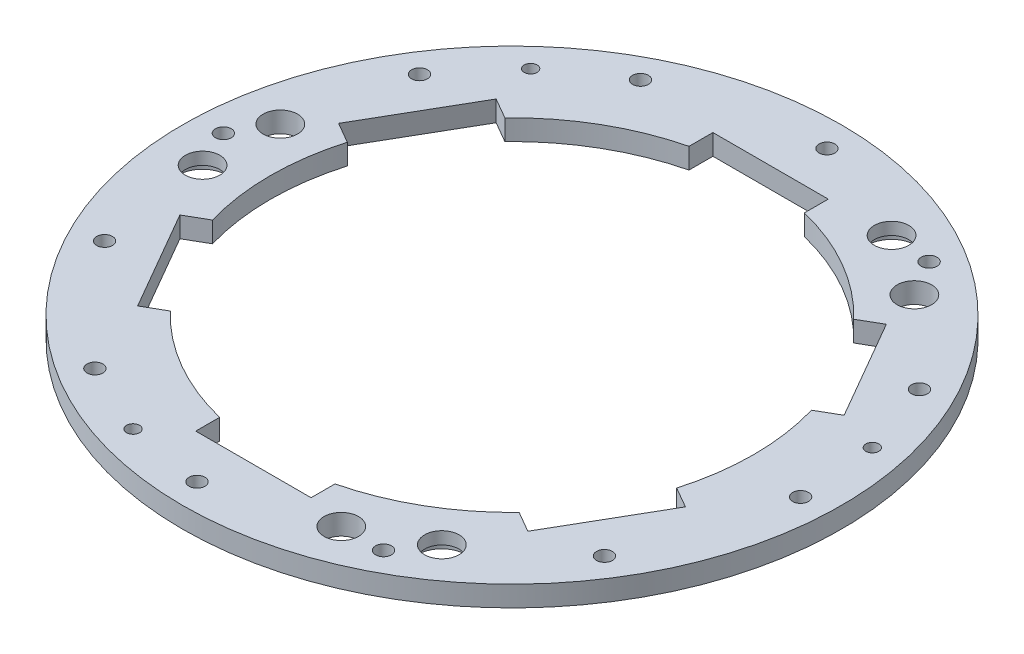
SolidWorks part; units mm, degrees
material "6061 Alloy"
ref_plane "Front Plane" through (0, 0, 0) normal (0, 0, 1) x (1, 0, 0)
ref_plane "Top Plane" through (0, 0, 0) normal (0, 1, 0) x (1, 0, 0)
ref_plane "Right Plane" through (0, 0, 0) normal (1, 0, 0) x (0, 0, -1)
sketch "Sketch1" plane through (0, 0, 0) normal (0, 1, 0) x (1, 0, 0)
  line L0 (-13.335, -54.2656) -> (-13.335, -58.1814)
  line L1 (13.335, -54.2656) -> (13.335, -58.1814)
  line L2 (-13.335, -59.7901) -> (13.335, -59.7901)
  line L3 (13.335, -58.1814) -> (13.335, -59.7901)
  line L4 (-13.335, -58.1814) -> (-13.335, -59.7901)
  line L5 (0, 0) -> (-65.7887, -5.7558) construction
  line L6 (0, 0) -> (-3.0468, -69.7835) construction
  line L7 (0, 0) -> (0, -26.4169) construction
  line L8 (0, 0) -> (-21.0043, -66.6171) construction
  line L9 (-65.0367, 11.4677) -> (0, 0) construction
  circle A0 centre (0, 0) radius 55.88
  circle A1 centre (0, 0) radius 76.2
  circle A2 centre (0, 0) radius 59.69
  circle A3 centre (-3.0468, -69.7835) radius 1.8288
  circle A4 centre (-65.7887, -5.7558) radius 3.9903
  circle A5 centre (-65.0367, 11.4677) radius 3.9903
  circle A6 centre (-21.0043, -66.6171) radius 1.5
  point P24 (0, 0)
  point P29 (0, 0)
  dimension "D1" = 111.76
  dimension "D2" = 152.4
  dimension "D8" = 3.6576
  dimension "D11" = 7.9807
  dimension "D12" = 7.9807
  dimension "D16" = 3
  dimension "D4" = 13.335
  dimension "D5" = 13.335
  dimension "D7" = 69.85
  dimension "D6" = 5.5245
  dimension "D9" = 66.04
  dimension "D10" = 82.5
  dimension "D15" = 15
  dimension "D13" = 2.5
  dimension "D14" = 15
  dimension "D3" = 3.81
extrude "Boss-Extrude1" add sketch "Sketch1" along normal blind 4.7625 contours L1 A2 L0 A0 | A1 A2 A0 region at (-15.0127, 0, 56.2235) region at (-74.0447, 0, 0)
pattern_circular "CirPattern1" count 6 over 360 about axis through (0, 4.7625, 0) along (0, 1, 0) of face at (-13.335, 2.3813, 57.0278) of face at (13.335, 2.3813, 57.0278) of face at (0, 2.3813, 59.7901)
pattern_circular "CirPattern7" count 12 over 360 about axis through (0, 4.7625, 0) along (0, 1, 0) of face at (-3.0468, 4.7625, 71.6123)
sketch "Sketch4" plane through (0, 0, 0) normal (0, -1, 0) x (1, 0, 0)
  line L0 (0, 0) -> (-65.7887, 5.7558) construction
  line L1 (0, 0) -> (0, -39.7137) construction
  circle A0 centre (-65.7887, 5.7558) radius 5.588
  circle A2 centre (-65.7887, 5.7558) radius 3.9903 construction
  circle A3 centre (-65.7887, 5.7558) radius 3.9903
  point P12 (0, 0)
  dimension "D2" = 11.176
extrude "Cut-Extrude1" cut sketch "Sketch4" against normal blind 1.905 contours A0 region at (-71.2186, 0, 5.7558)
pattern_circular "CirPattern2" count 3 over 360 about axis through (0, 0, 0) along (0, 1, 0) of face at (-65.7887, 4.7625, 9.7461) of face at (-65.7887, 1.905, 1.7654) of face at (-65.7887, 1.905, 0.1678) of face at (-65.0367, 4.7625, -7.4774) of face at (-21.0043, 4.7625, 68.1171)
sketch "Sketch5" plane through (0, 4.7625, 0) normal (0, 1, 0) x (1, 0, 0)
  line L0 (0, 0) -> (-20.0894, -55.1952)
  line L1 (0, 0) -> (0, -18.6852)
  line L2 (-16.5968, -53.0258) -> (-18.2257, -57.5011) construction
  line L3 (-18.2257, -57.5011) -> (-22.9993, -55.7636) construction
  line L4 (-22.9993, -55.7636) -> (-21.3704, -51.2884) construction
  line L5 (-59.7924, -7.9638) -> (-55.1022, -7.1368)
  line L6 (-54.2201, -12.1397) -> (-58.9103, -12.9667)
  line L7 (-58.9103, -12.9667) -> (-59.7924, -7.9638)
  line L8 (-36.7931, 47.7998) -> (-33.7318, 44.1515)
  line L9 (-37.6233, 40.8862) -> (-40.6846, 44.5345)
  line L10 (-40.6846, 44.5345) -> (-36.7931, 47.7998)
  line L11 (22.9993, 55.7636) -> (21.3704, 51.2884)
  line L12 (16.5968, 53.0258) -> (18.2257, 57.5011)
  line L13 (18.2257, 57.5011) -> (22.9993, 55.7636)
  line L14 (59.7924, 7.9638) -> (55.1022, 7.1368)
  line L15 (54.2201, 12.1397) -> (58.9103, 12.9667)
  line L16 (58.9103, 12.9667) -> (59.7924, 7.9638)
  line L17 (36.7931, -47.7998) -> (33.7318, -44.1515)
  line L18 (37.6233, -40.8862) -> (40.6846, -44.5345)
  line L19 (40.6846, -44.5345) -> (36.7931, -47.7998)
  circle A0 centre (0, 0) radius 55.5625
  circle A1 centre (0, 0) radius 58.7375 construction
  circle A2 centre (0, 0) radius 55.5625
  circle A3 centre (0, 0) radius 55.5625
  circle A4 centre (0, 0) radius 55.5625
  circle A5 centre (0, 0) radius 55.5625
  circle A6 centre (0, 0) radius 55.5625
  circle A7 centre (0, 0) radius 76.2
  circle A8 centre (0, 0) radius 63.5
  point P38 (0, 0)
  dimension "D1" = 111.125
  dimension "D3" = 20
  dimension "D4" = 2.54
  dimension "D5" = 4.7625
  dimension "D6" = 2.54
  dimension "D2" = 3.175
  dimension "D8" = 12.7
  dimension "D7" = 6
split line "Split Line1" [suppressed]
equation "\"Middle Coupler Inner Daimeter\"= 3.875in"
equation "\"Middle Coupler  Wall Thickness\" = 0.25in"
equation "\"Middle Coupler Bottom Thickness\"= 0.2in"
equation "\"Bearing Rail Offset\"= 0.45in"
equation "\"3-56 UNF Tap\"= 0.089in"
equation "\"3-56 UNF Clearance\"= 0.104in"
equation "\"Ball Bearing Distance\"= 0.03in"
equation "\"D1@Sketch1\"=\"Middle Coupler Inner Daimeter\"+0.5+0.0125*2in"
equation "\"TCA Outer Diameter\" = 6in"
equation "\"D2@Sketch1\"=\"TCA Outer Diameter\""
equation "\"D4@Sketch1\"=0.50 + (0.05/2)"
equation "\"D5@Sketch1\"=\"D4@Sketch1\""
equation "\"D7@Sketch1\"=(\"D2@Sketch1\"-0.5)/2"
equation "\"D8@Sketch1\"=\"6-32 Clearance\""
equation "\"Interstage Aeroframe Wall Thickness\" = 0.072in"
equation "\"Compression Spring OD\"= 0.42in"
equation "\"10-24 Tap\"= 0.157in"
equation "\"10-24 Clearance\"= 0.196in"
equation "\"D2@Sketch4\"=\"Compression Spring OD\"+0.02"
equation "\"D3@Sketch1\"=0.125in+(0.05/2)"
equation "\"Lower Stage Fuselage Wall Thickness\" = 0.25in"
equation "\"6-32 Tap\" = 0.107in"
equation "\"1/4-20 Tap\" = 0.201in"
equation "\"3-48 Tap\"= 0.079in"
equation "\"12-24 Tap\" = 0.177in"
equation "\"3-48 Clearance\" = 0.104in"
equation "\"6-32 Clearance\" = 0.144"
equation "\"D6@Sketch1\"=3/16 + 0.03"
equation "\"D9@Sketch1\"=(\"D2@Sketch1\"+\"D1@Sketch1\")/4+0.1-.1"
equation "\"D1@Sketch5\"=\"Middle Coupler Inner Daimeter\"+0.5"
equation "\"D5@Sketch5\"=3/16"
equation "\"D6@Sketch5\"=\"D4@Sketch5\""
equation "\"D1@Boss-Extrude1\"=3/16"
equation "\"4-40 Tap\"= 0.089in"
equation "\"4-40 Clearance\" = 0.116in"
equation "\"12-24 Major Diameter\"= 0.216in"
equation "\"D16@Sketch1\"=3mm"
equation "\"D11@Sketch1\"=\"D12@Sketch1\""
